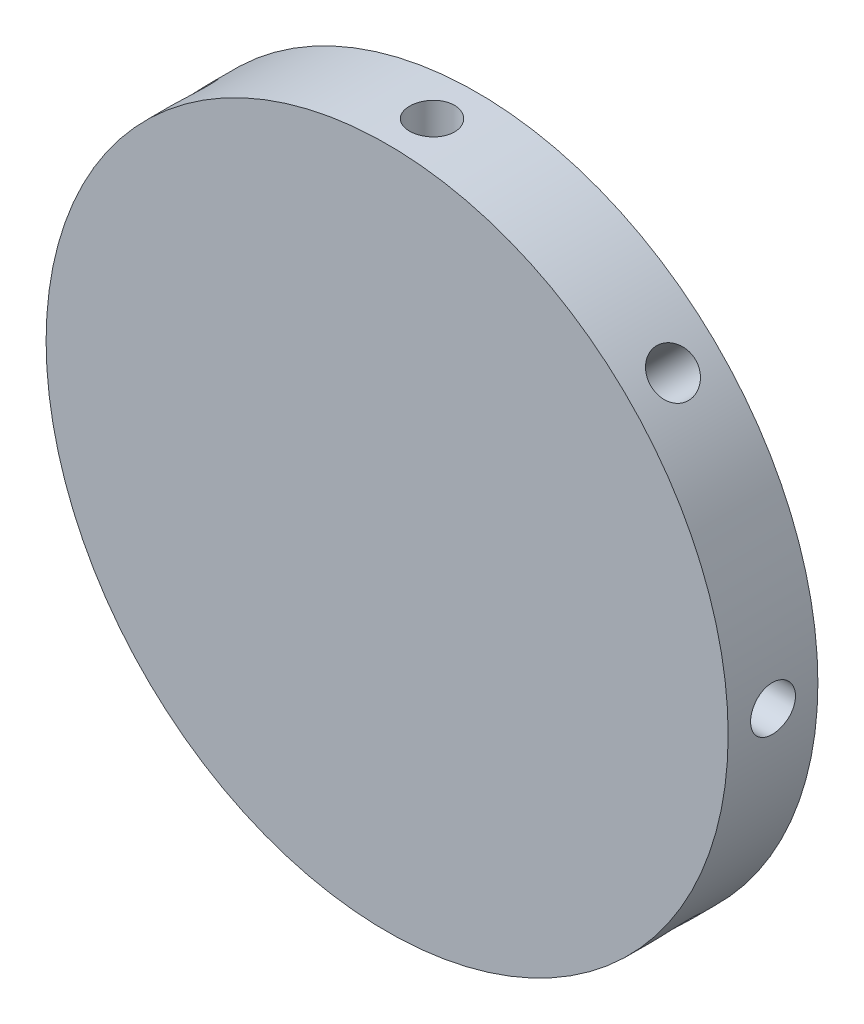
SolidWorks part; units mm, degrees
ref_plane "Front Plane" through (0, 0, 0) normal (0, 0, 1) x (1, 0, 0)
ref_plane "Top Plane" through (0, 0, 0) normal (0, 1, 0) x (1, 0, 0)
ref_plane "Right Plane" through (0, 0, 0) normal (1, 0, 0) x (0, 0, -1)
sketch "Sketch1" plane through (0, 0, 0) normal (0, 0, 1) x (1, 0, 0)
  circle A0 centre (0, 0) radius 38
  dimension "D1" = 76
extrude "Boss-Extrude1" add sketch "Sketch1" along normal blind 10
ref_plane "Attachments" through (0, 38, 0) normal (0, 1, 0) x (1, 0, 0)
sketch "Sketch2" plane through (0, 38, 0) normal (0, 1, 0) x (1, 0, 0)
  line L0 (0, 0) -> (0, -5) construction
  circle A1 centre (0, -5) radius 2.5
  dimension "D2" = 5
  dimension "D1" = 5
extrude "Cut-Extrude1" cut sketch "Sketch2" against normal blind 10
pattern_circular "CirPattern1" count 8 over 360 about axis through (0, 0, 10) along (0, 0, -1) of "Cut-Extrude1"
